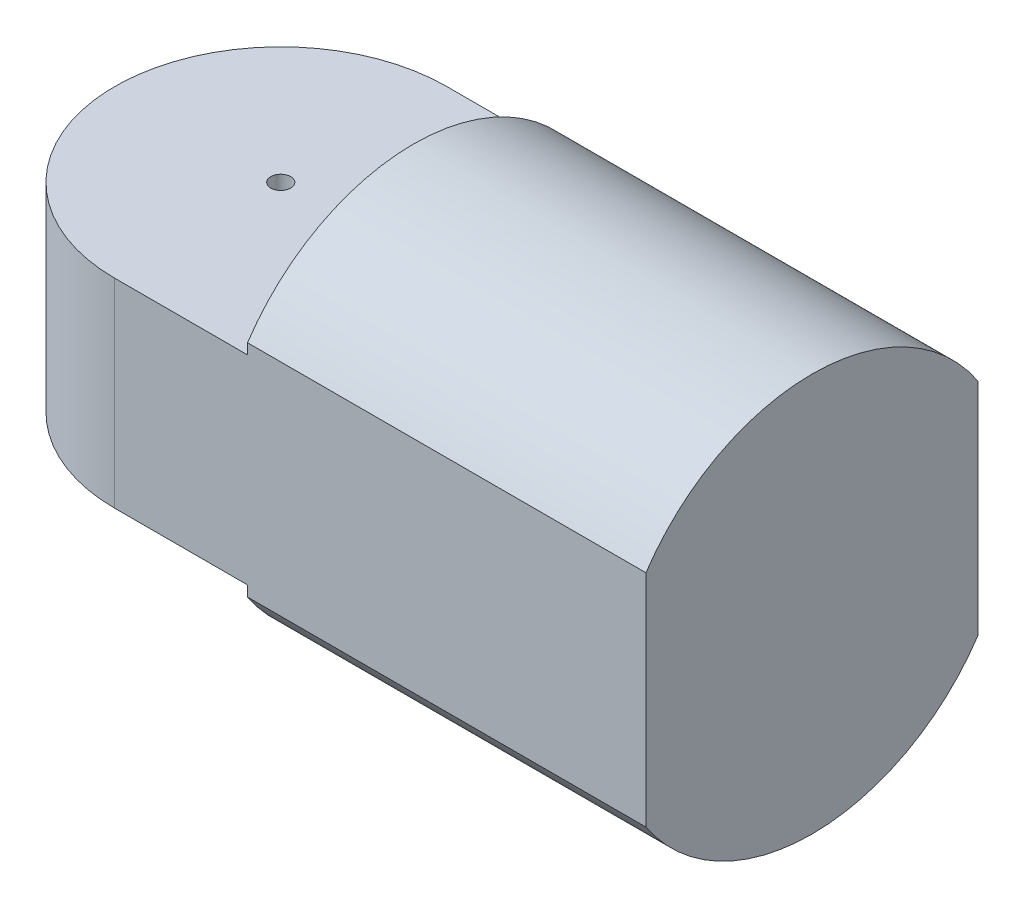
SolidWorks part; units mm, degrees
ref_plane "Front Plane" through (0, 0, 0) normal (0, 0, 1) x (1, 0, 0)
ref_plane "Top Plane" through (0, 0, 0) normal (0, 1, 0) x (1, 0, 0)
ref_plane "Right Plane" through (0, 0, 0) normal (1, 0, 0) x (0, 0, -1)
sketch "Sketch1" plane through (0, 0, 0) normal (1, 0, 0) x (0, 0, -1)
  line L0 (0, 60) -> (0, -60) construction
  line L1 (-50, 33.1662) -> (-50, -33.1662)
  line L2 (50, 33.1662) -> (50, -33.1662)
  circle A0 centre (0, 0) radius 60
  dimension "D1" = 120
  dimension "D2" = 50
  dimension "D3" = 50
extrude "Boss-Extrude1" add sketch "Sketch1" against normal blind 120 contours L0 A0 L1 | A0 L0 L2 region at (0, 0, -22.9942) region at (0, 0, 22.9942)
sketch "Sketch2" plane through (-120, 0, 0) normal (-1, 0, 0) x (0, 0, 1)
  line L0 (-50, -33.1662) -> (-50, 33.1662) construction
  line L1 (50, 30) -> (-50, 30)
  line L2 (50, 30) -> (50, -30)
  line L3 (50, -30) -> (-50, -30)
  line L4 (-50, 30) -> (-50, -30)
  line L5 (50, 30) -> (-50, -30) construction
  line L6 (50, -30) -> (-50, 30) construction
  point P0 (0, 0)
  dimension "D1" = 60
extrude "Boss-Extrude2" add sketch "Sketch2" along normal blind 90
sketch "Sketch3" plane through (0, 30, 0) normal (0, 1, 0) x (1, 0, 0)
  line L0 (-210, 50) -> (-120, 50) construction
  line L1 (-210, -50) -> (-120, -50) construction
  line L2 (-210, -50) -> (-210, 50) construction
  line L3 (-160, 50) -> (-210, 50)
  line L4 (-210, 50) -> (-210, -50)
  line L5 (-210, -50) -> (-160, -50)
  arc A0 (-160, 50) -> (-160, -50) centre (-160, 0) ccw
  line M2 (-120, 50) -> (-210, 50)
  line M3 (-210, 50) -> (-210, -50)
  line M4 (-210, -50) -> (-120, -50)
  dimension "D1" = 50
extrude "Cut-Extrude1" cut sketch "Sketch3" against normal through all contours A0 L4 M4 | A0 M2 M3 region at (-198.8316, 30, -38.8316) region at (-198.8316, 30, 38.8316)
sketch "Sketch4" plane through (0, 30, 0) normal (0, 1, 0) x (1, 0, 0)
  line L0 (-210, 0) -> (-160, 0) construction
  arc A0 (-160, 50) -> (-160, -50) centre (-160, 0) ccw construction
  circle A1 centre (-160, 0) radius 3
  dimension "D2" = 6
  dimension "D1" = 50
extrude "Cut-Extrude2" cut sketch "Sketch4" against normal blind 6
